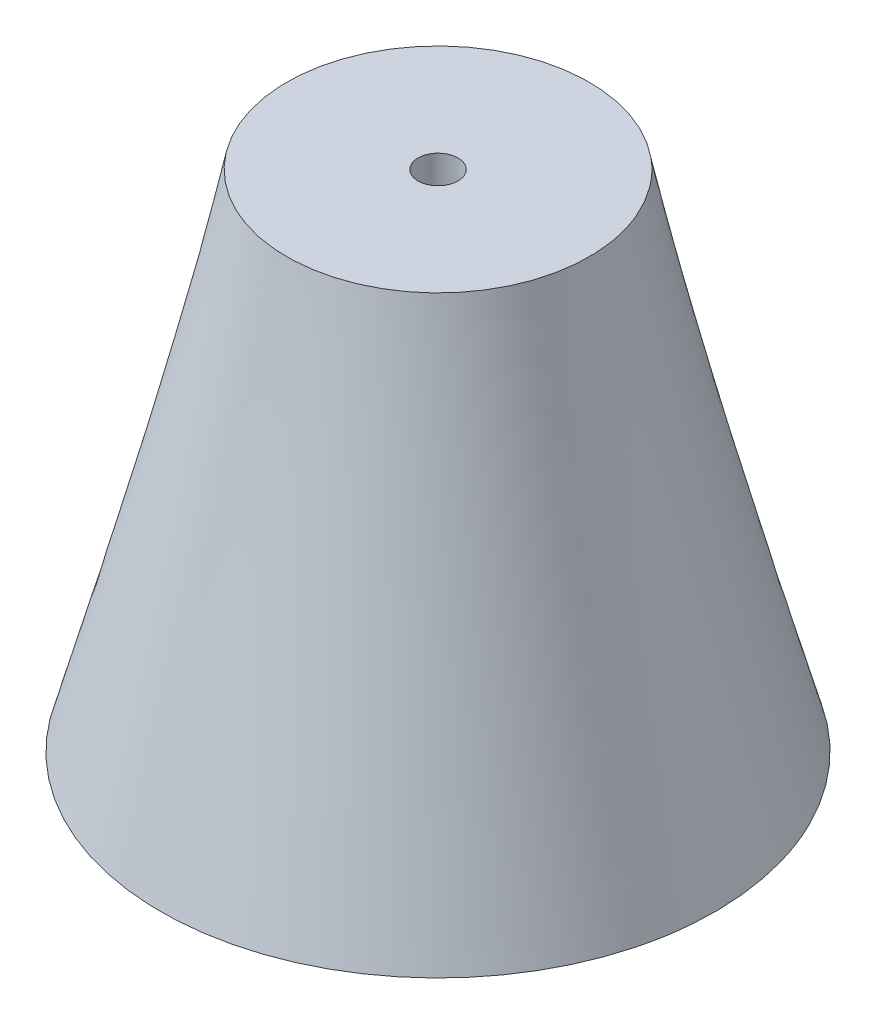
SolidWorks part; units mm, degrees
ref_plane "Front Plane" through (0, 0, 0) normal (0, 0, 1) x (1, 0, 0)
ref_plane "Top Plane" through (0, 0, 0) normal (0, 1, 0) x (1, 0, 0)
ref_plane "Right Plane" through (0, 0, 0) normal (1, 0, 0) x (0, 0, -1)
sketch "Sketch4" plane through (0, 0, 0) normal (0, 1, 0) x (1, 0, 0)
  circle A0 centre (0, 0) radius 27.5
  dimension "D1" = 55
ref_plane "Plane1" through (0, 50, 0) normal (0, -1, 0) x (-1, 0, 0)
sketch "Sketch7" plane through (0, 50, 0) normal (0, -1, 0) x (-1, 0, 0)
  circle A0 centre (0, 0) radius 15
  dimension "D1" = 30
loft "Loft2" add profiles "Sketch4", "Sketch7" connector at (-27.3646, 0, 2.7256) connector at (-13.0154, 50, 7.4564)
sketch "Sketch15" plane through (0, 50, 0) normal (0, -1, 0) x (-1, 0, 0)
  circle A0 centre (0, 0) radius 1.9802
  dimension "D1" = 3.9604
extrude "Cut-Extrude1" cut sketch "Sketch15" along normal blind 10
ref_plane "Plane2" through (0, 0, 0) normal (0, -1, 0) x (-1, 0, 0)
